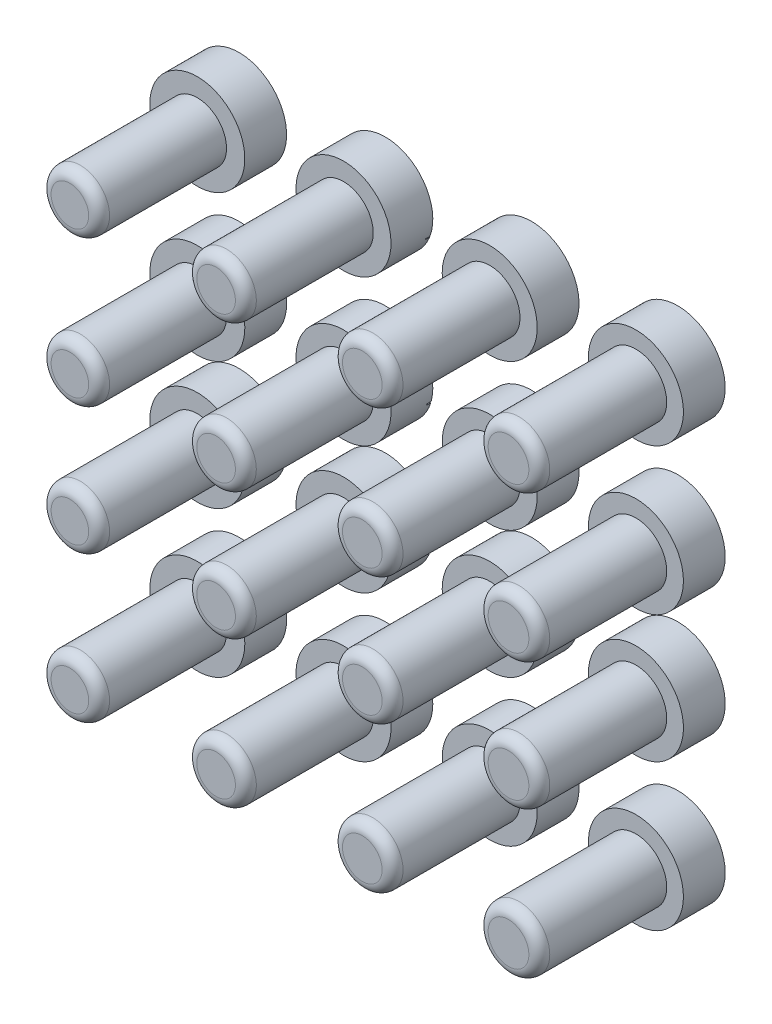
SolidWorks part; units mm, degrees
ref_plane "Ebene vorne" through (0, 0, 0) normal (0, 0, 1) x (1, 0, 0)
ref_plane "Ebene oben" through (0, 0, 0) normal (0, 1, 0) x (1, 0, 0)
ref_plane "Ebene rechts" through (0, 0, 0) normal (1, 0, 0) x (0, 0, -1)
sketch "Sketch1" plane through (0, 0, 0) normal (0, 0, 1) x (1, 0, 0)
  line L0 (55, 0) -> (-55, 0) construction
  line L1 (-11.1378, -6.55) -> (20.9044, -6.55) construction
  line L2 (0, 0) -> (0, -15.2824) construction
  circle A4 centre (-10.5, -3.5) radius 1.4
  circle A5 centre (-3.5, -3.5) radius 1.425
  circle A6 centre (3.5, -3.5) radius 1.45
  circle A7 centre (10.5, -3.5) radius 1.475
  circle A8 centre (10.5, 3.5) radius 1.475
  circle A9 centre (3.5, 3.5) radius 1.45
  circle A10 centre (-3.5, 3.5) radius 1.425
  circle A11 centre (-10.5, 3.5) radius 1.4
  circle A12 centre (3.5, -16.6) radius 1.45
  circle A13 centre (10.5, -16.6) radius 1.475
  circle A14 centre (10.5, -9.6) radius 1.475
  circle A15 centre (3.5, -9.6) radius 1.45
  circle A16 centre (-3.5, -16.6) radius 1.425
  circle A17 centre (-3.5, -9.6) radius 1.425
  circle A18 centre (-10.5, -9.6) radius 1.4
  circle A19 centre (-10.5, -16.6) radius 1.4
  dimension "D1" = 2.8
  dimension "D2" = 2.85
  dimension "D3" = 2.9
  dimension "D4" = 2.95
  dimension "D14" = 2.85
  dimension "D15" = 2.85
  dimension "D16" = 2.8
  dimension "D17" = 2.8
  dimension "D5" = 7
  dimension "D6" = 7
  dimension "D7" = 7
  dimension "D8" = 0
  dimension "D9" = 0
  dimension "D10" = 0
  dimension "D11" = 3.5
  dimension "D12" = 3.5
  dimension "D13" = 6.55
sketch "Sketch4" plane through (0, 0, 0) normal (0, 0, 1) x (1, 0, 0)
  line L0 (55, 0) -> (-55, 0) construction
  line L1 (12.9219, -6.55) -> (-14.0212, -6.55) construction
  circle A0 centre (-10.5, -3.5) radius 2.275
  circle A1 centre (-3.5, -3.5) radius 2.275
  circle A2 centre (3.5, -3.5) radius 2.275
  circle A3 centre (10.5, -3.5) radius 2.275
  circle A4 centre (-10.5, 3.5) radius 2.275
  circle A5 centre (-3.5, 3.5) radius 2.275
  circle A6 centre (3.5, 3.5) radius 2.275
  circle A7 centre (10.5, 3.5) radius 2.275
  circle A16 centre (10.5, -16.6) radius 2.275
  circle A17 centre (3.5, -16.6) radius 2.275
  circle A18 centre (-3.5, -16.6) radius 2.275
  circle A19 centre (-10.5, -16.6) radius 2.275
  circle A20 centre (10.5, -9.6) radius 2.275
  circle A21 centre (3.5, -9.6) radius 2.275
  circle A22 centre (-3.5, -9.6) radius 2.275
  circle A23 centre (-10.5, -9.6) radius 2.275
  dimension "D1" = 4.55
  dimension "D2" = 4.55
  dimension "D3" = 4.55
  dimension "D4" = 4.55
  dimension "D5" = 6.55
extrude "Boss-Extrude4" add sketch "Sketch4" against normal blind 2
extrude "Boss-Extrude5" add sketch "Sketch1" along normal blind 6.1
sketch "Sketch6" plane through (0, 0, 0) normal (0, 0, 1) x (1, 0, 0)
  text T0 "2.95      2.9      2.85       2.8" font "Century Gothic" height 1.5
extrude "Cut-Extrude1" cut sketch "Sketch6" against normal blind 6.1 from offset 1.8 offset against normal yes
fillet "Fillet1" radius 0.5 1 edges at (-9.1, -3.5, 6.1)
fillet "Fillet2" radius 0.5 1 edges at (-2.075, -3.5, 6.1)
fillet "Fillet3" radius 0.5 1 edges at (4.95, -3.5, 6.1)
fillet "Fillet4" radius 0.5 1 edges at (11.975, -3.5, 6.1)
fillet "Fillet5" radius 0.5 1 edges at (9.025, 3.5, 6.1)
fillet "Fillet6" radius 0.5 1 edges at (2.05, 3.5, 6.1)
fillet "Fillet7" radius 0.5 1 edges at (-4.925, 3.5, 6.1)
fillet "Fillet8" radius 0.5 1 edges at (-11.9, 3.5, 6.1)
sketch "Sketch7" plane through (0, 0, 0) normal (0, 0, 1) x (1, 0, 0)
  text T0 "2.95      2.9      2.85      2.8" font "Century Gothic" height 1.5
extrude "Cut-Extrude2" cut sketch "Sketch7" against normal blind 1 from offset 1.8 offset against normal yes
fillet "Fillet14" radius 0.5 1 edges at (11.975, -16.6, 6.1)
fillet "Fillet15" radius 0.5 1 edges at (4.95, -16.6, 6.1)
fillet "Fillet16" radius 0.5 1 edges at (-4.925, -16.6, 6.1)
fillet "Fillet17" radius 0.5 1 edges at (-11.9, -16.6, 6.1)
fillet "Fillet18" radius 0.5 1 edges at (9.025, -9.6, 6.1)
fillet "Fillet19" radius 0.5 1 edges at (2.05, -9.6, 6.1)
fillet "Fillet20" radius 0.5 1 edges at (-2.075, -9.6, 6.1)
fillet "Fillet21" radius 0.5 1 edges at (-9.1, -9.6, 6.1)
sketch "Sketch10" plane through (0, 0, 0) normal (0, 0, 1) x (1, 0, 0)
  text T0 "2.95      2.9      2.85      2.8" font "Century Gothic" height 1.5
  text T1 "2.95      2.9      2.85      2.8" font "Century Gothic" height 1.5
extrude "Cut-Extrude4" cut sketch "Sketch10" against normal blind 0.3 from offset 1.8 offset against normal yes
